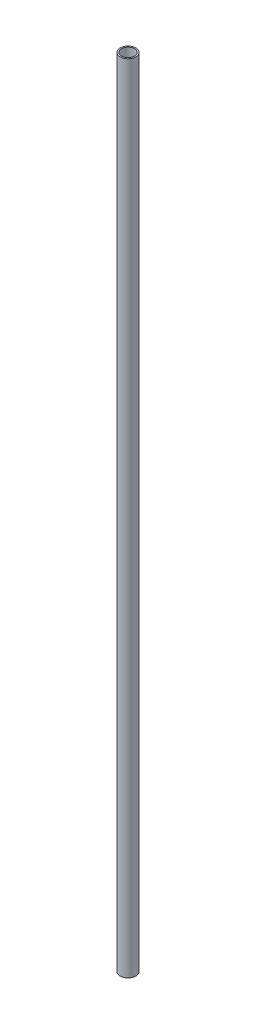
SolidWorks part; units mm, degrees
material "Carbon Fiber (2)"
ref_plane "Front Plane" through (0, 0, 0) normal (0, 0, 1) x (1, 0, 0)
ref_plane "Top Plane" through (0, 0, 0) normal (0, 1, 0) x (1, 0, 0)
ref_plane "Right Plane" through (0, 0, 0) normal (1, 0, 0) x (0, 0, -1)
sketch "Sketch1" plane through (0, 0, 0) normal (0, 1, 0) x (1, 0, 0)
  circle A0 centre (0, 0) radius 4.953
  circle A1 centre (0, 0) radius 5.9944
  dimension "D1" = 9.906
  dimension "D2" = 11.9888
extrude "Boss-Extrude1" add sketch "Sketch1" along normal blind 609.6
